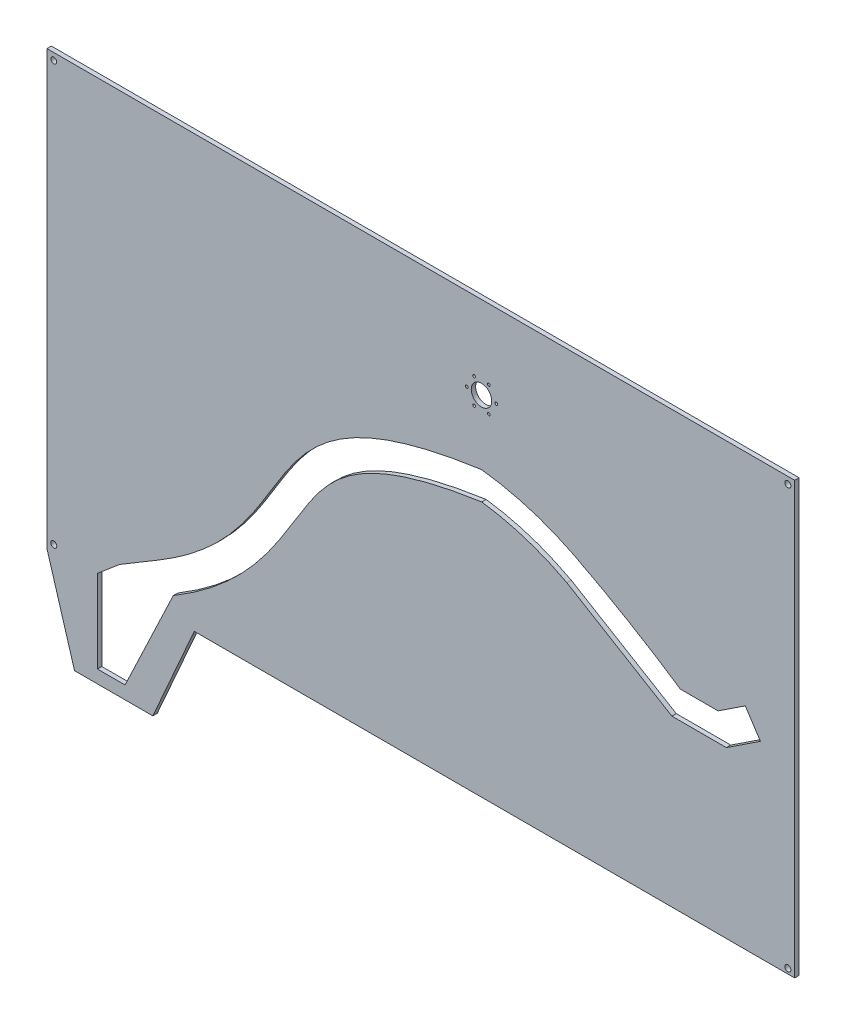
SolidWorks part; units mm, degrees
ref_plane "前视基准面" through (0, 0, 0) normal (0, 0, 1) x (1, 0, 0)
ref_plane "上视基准面" through (0, 0, 0) normal (0, 1, 0) x (1, 0, 0)
ref_plane "右视基准面" through (0, 0, 0) normal (1, 0, 0) x (0, 0, -1)
sketch "Sketch1" plane through (0, 0, 0) normal (0, 0, 1) x (1, 0, 0)
  line L0 (86.3892, 46.5642) -> (136.3892, 46.5642) construction
  line L1 (136.3892, 46.5642) -> (169.6686, 68.4983) construction
  line L2 (-475, -100) -> (-518.0311, -125.7444)
  line L3 (-596.8168, -150) -> (-566.8168, -250)
  line L4 (81.7745, 31.5642) -> (140.8878, 31.5642)
  line L5 (-467.2989, -112.8722) -> (-510.33, -138.6166) construction
  line L6 (140.8878, 31.5642) -> (177.9233, 55.9739)
  line L7 (-459.5978, -125.7444) -> (-511.9755, -236)
  line L8 (-436.8168, -147.9944) -> (215.0808, -147.9944)
  line L9 (215.0808, -147.9944) -> (215.0808, 320)
  line L10 (215.0808, 320) -> (-596.8168, 320)
  line L11 (-596.8168, -150) -> (-596.8168, 320)
  line L12 (215.0808, -147.9944) -> (-596.8168, 320) construction
  line L13 (215.0808, 320) -> (-596.8168, -150) construction
  line L14 (-518.0311, -125.7444) -> (-459.5978, -125.7444) construction
  line L15 (-436.8168, -147.9944) -> (-481.8168, -250)
  line L16 (-566.8168, -250) -> (-481.8168, -250)
  line L17 (90.9712, 61.5642) -> (131.8907, 61.5642)
  line L18 (-511.9755, -236) -> (-541.9755, -236)
  line L19 (-541.9755, -236) -> (-541.9755, -146)
  line L20 (-518.0311, -125.7444) -> (-541.9755, -146)
  line L21 (-32.3237, 100) -> (135.1953, 100) construction
  line L22 (-25, 130) -> (125, 130) construction
  line L23 (-28.6108, 115) -> (130.0228, 115) construction
  line L24 (131.8907, 61.5642) -> (161.4139, 81.0227)
  line L25 (177.9233, 55.9739) -> (161.4139, 81.0227)
  line L26 (-21.7014, 128.3139) -> (-25, 130)
  line L27 (-32.3237, 100) -> (81.7745, 31.5642)
  arc A0 (-125, 160) -> (-25, 130) centre (-159.8893, -137.9643) cw
  arc A1 (-28.6108, 115) -> (86.3892, 46.5642) centre (-559.3589, -907.7137) cw construction
  arc A2 (-124.7147, 129.7347) -> (-32.3237, 100) centre (-159.8893, -137.9643) cw
  circle A3 centre (-125, 230) radius 16 construction
  arc A4 (-124.84, 144.8723) -> (-28.6108, 115) centre (-159.8893, -137.9643) cw construction
  arc A5 (-21.7014, 128.3139) -> (90.9712, 61.5642) centre (-559.3589, -907.7137) cw
  circle A6 centre (-589.3757, -142.5578) radius 3.2924
  circle A7 centre (207.6422, -142.5578) radius 3.2924
  circle A8 centre (207.6422, 312.5578) radius 3.2944
  circle A9 centre (-589.3757, 312.5578) radius 3.1635
  arc A10 (135.1953, 100) -> (187.8618, 132.897) centre (303.6181, -111.0302) cw construction
  arc A11 (130.0228, 115) -> (181.4309, 146.4485) centre (303.6181, -111.0302) cw construction
  arc A12 (125, 130) -> (175, 160) centre (303.6181, -111.0302) cw construction
  arc A13 (-35.5202, 101.6861) -> (81.7745, 31.5642) centre (-559.3589, -907.7137) cw construction
  circle A14 centre (-141, 230) radius 1.5
  circle A15 centre (-133, 243.8564) radius 1.5
  circle A16 centre (-117, 243.8564) radius 1.5
  circle A17 centre (-109, 230) radius 1.5
  circle A18 centre (-117, 216.1436) radius 1.5
  circle A19 centre (-133, 216.1436) radius 1.5
  circle A20 centre (-125, 230) radius 11.1125
  spline S0 degree 3 poles (-475, -100) (-419.5406, -66.8201) (-329.5908, 43.116) (-307.6356, 134.2871) (-125, 160) knots 0 0 0 0 0.312224 1 1 1 1
  spline S1 degree 1 poles (-459.5978, -125.7444) (-124.7147, 129.7347) knots 0 0 1 1 construction
  spline S2 degree 3 poles (-459.5978, -125.7444) (-458.1292, -124.8657) (-455.1858, -123.0815) (-449.4714, -119.5247) (-442.5555, -115.0462) (-434.6362, -109.6397) (-424.5564, -102.3861) (-412.8294, -93.2453) (-400.0558, -82.1905) (-388.4865, -71.0922) (-374.5374, -56.3046) (-359.6201, -37.9792) (-344.8908, -16.7676) (-332.3401, 3.2457) (-321.0552, 21.7964) (-310.226, 38.6648) (-299.0796, 53.8348) (-286.8128, 67.5146) (-272.4318, 80.0885) (-257.6527, 89.9241) (-243.4982, 97.442) (-231.5651, 102.8866) (-218.1727, 108.1127) (-203.191, 113.0878) (-189.2817, 116.9961) (-177.2434, 119.9629) (-167.7458, 122.1041) (-157.766, 124.1573) (-149.0369, 125.7919) (-141.7993, 127.0518) (-136.2431, 127.9723) (-131.5022, 128.7191) (-127.6487, 129.3032) (-125.6903, 129.5925) (-124.7147, 129.7347) knots 0 0 0 0 0.007773 0.015545 0.03109 0.046636 0.062181 0.093271 0.124361 0.155452 0.186542 0.248723 0.310904 0.373084 0.435265 0.497446 0.559626 0.621807 0.683988 0.746169 0.777259 0.808349 0.83944 0.87053 0.90162 0.917166 0.932711 0.948256 0.963801 0.971574 0.979346 0.987119 0.991005 0.994892 0.994892 0.994892 0.994892
  spline S3 degree 1 poles (-467.2989, -112.8722) (-124.84, 144.8723) knots 0 0 1 1 construction
  spline S4 degree 3 poles (-467.2989, -112.8722) (-465.8766, -112.0213) (-463.025, -110.2926) (-457.4973, -106.8516) (-450.8174, -102.5249) (-443.1848, -97.3122) (-433.4896, -90.3317) (-422.2436, -81.559) (-410.0336, -70.981) (-398.9994, -60.3828) (-385.707, -46.2708) (-371.4731, -28.7597) (-357.2741, -8.2881) (-344.9599, 11.3612) (-333.6257, 29.9919) (-322.417, 47.4318) (-310.4985, 63.6121) (-297.0179, 78.5777) (-281.0248, 92.4603) (-264.7088, 103.2127) (-249.3105, 111.3089) (-236.4572, 117.1105) (-222.1723, 122.621) (-206.3349, 127.8161) (-191.7467, 131.8615) (-179.1859, 134.915) (-169.3063, 137.1107) (-158.9544, 139.2089) (-149.9221, 140.8739) (-142.4479, 142.1541) (-136.7117, 143.0887) (-130.8627, 143.9946) (-126.8382, 144.5862) (-124.84, 144.8723) knots 0 0 0 0 0.007793 0.015586 0.031173 0.046759 0.062345 0.093518 0.12469 0.155863 0.187036 0.249381 0.311726 0.374071 0.436417 0.498762 0.561107 0.623452 0.685798 0.748143 0.779315 0.810488 0.841661 0.872833 0.904006 0.919592 0.935179 0.950765 0.966351 0.974144 0.981937 0.989731 0.997524 0.997524 0.997524 0.997524 construction
  point P38 (-190, 85.5025)
  point P62 (-125, 230)
  dimension "D5" = 300
  dimension "D8" = 15
  dimension "D14" = 470
  dimension "D18" = 30
  dimension "D19" = 30
  dimension "D20" = 90
  dimension "D21" = 85
  dimension "D22" = 651.8975
  dimension "D23" = 70
  dimension "D24" = 100
  dimension "D26" = 6
  dimension "D27" = 3
  dimension "D28" = 22.225
  dimension "D1" = 105
  dimension "D2" = 100
  dimension "D3" = 350
  dimension "D4" = 260
  dimension "D6" = 100
  dimension "D7" = 30
  dimension "D9" = 15
  dimension "D10" = 115
  dimension "D11" = 50
  dimension "D13" = 15
  dimension "D15" = 190
  dimension "D16" = 320
  dimension "D17" = 100
  dimension "D25" = 811.9
  dimension "D12" = 30
extrude "Boss-Extrude1" add sketch "Sketch1" along normal blind 4.7625
